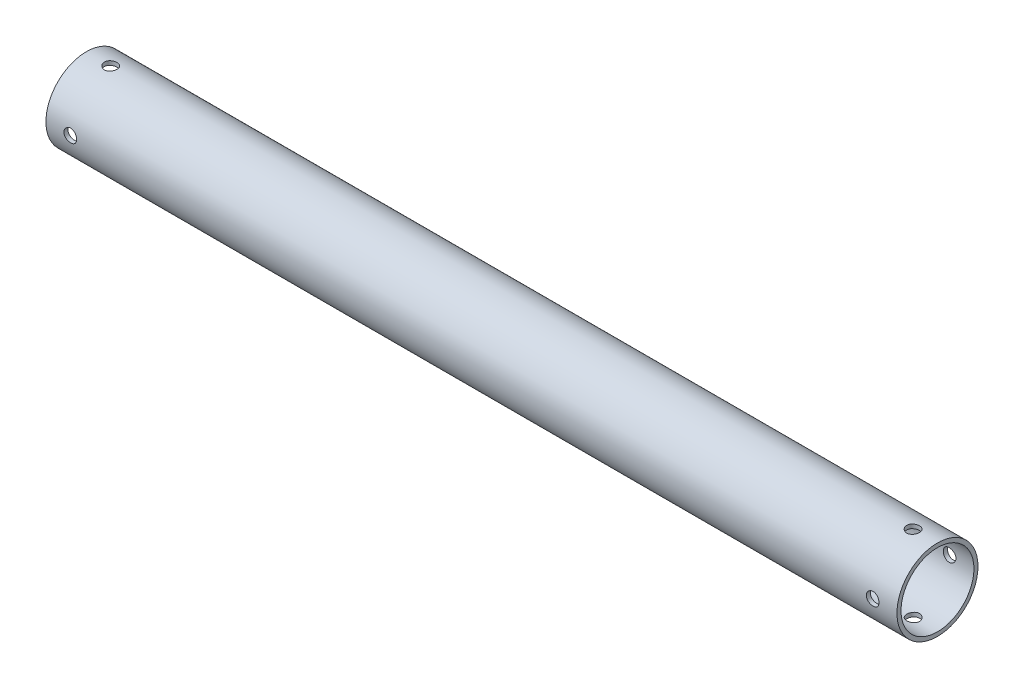
SolidWorks part; units mm, degrees
material "PC High Viscosity"
ref_plane "Front Plane" through (0, 0, 0) normal (0, 0, 1) x (1, 0, 0)
ref_plane "Top Plane" through (0, 0, 0) normal (0, 1, 0) x (1, 0, 0)
ref_plane "Right Plane" through (0, 0, 0) normal (1, 0, 0) x (0, 0, -1)
sketch "Sketch1" plane through (0, 0, 0) normal (1, 0, 0) x (0, 0, -1)
  circle A0 centre (0, 0) radius 15.875
  dimension "D1" = 31.75
extrude "Extrude-Thin1" add sketch "Sketch1" along normal mid plane 333.375 thin thin type one direction reverse wall 1.5875
sketch "Sketch2" plane through (0, 0, 0) normal (0, 0, 1) x (1, 0, 0)
  line L0 (-166.6875, -15.875) -> (166.6875, -15.875) construction
  line L1 (104.4125, -15.875) -> (125.4125, -15.875)
  line L2 (104.4125, -15.875) -> (104.4125, 15.875)
  line L3 (104.4125, 15.875) -> (125.4125, 15.875)
  line L4 (125.4125, -15.875) -> (125.4125, 15.875)
  line L5 (166.6875, 15.875) -> (-166.6875, 15.875) construction
  line L6 (166.6875, -15.875) -> (166.6875, 15.875) construction
  line L7 (0, 0) -> (0, 11.1276) construction
  line L8 (-125.4125, -15.875) -> (-125.4125, 15.875)
  line L9 (-104.4125, 15.875) -> (-125.4125, 15.875)
  line L10 (-104.4125, -15.875) -> (-104.4125, 15.875)
  line L11 (-104.4125, -15.875) -> (-125.4125, -15.875)
  line L13 (166.6875, -15.875) -> (164.3634, -15.875)
  line L14 (166.6875, -15.875) -> (166.6875, 15.875)
  line L15 (166.6875, 15.875) -> (164.3634, 15.875)
  line L16 (164.3634, -15.875) -> (164.3634, 15.875)
  dimension "D1" = 41.275
  dimension "D2" = 21
  dimension "D3" = 2.3241
sketch "Sketch3" plane through (0, 0, 0) normal (0, 0, 1) x (1, 0, 0)
  line L0 (166.6875, -14.2875) -> (166.6875, 14.2875) construction
  line L1 (-166.6875, 15.875) -> (-166.6875, -15.875) construction
  circle A0 centre (157.1625, 0) radius 2.4892
  circle A1 centre (-157.1625, 0) radius 2.4892
  dimension "D1" = 4.9784
  dimension "D2" = 9.525
  dimension "D3" = 9.525
extrude "Cut-Extrude1" cut sketch "Sketch3" against normal through all both and the other way through all
sketch "Sketch4" plane through (0, 0, 0) normal (0, 1, 0) x (1, 0, 0)
  line L0 (166.6875, -14.2875) -> (166.6875, 14.2875) construction
  line L1 (0, 15.875) -> (0, -15.875) construction
  line L2 (-154.6733, -15.875) -> (154.6733, -15.875) construction
  line L3 (154.6733, 15.875) -> (-154.6733, 15.875) construction
  circle A0 centre (157.1625, 0) radius 2.4892
  circle A1 centre (-157.1625, 0) radius 2.4892
  point P13 (-153.4268, 21.7052)
  dimension "D1" = 4.9784
  dimension "D2" = 9.525
extrude "Cut-Extrude2" cut sketch "Sketch4" against normal through all both and the other way through all
equation "\"D2@Sketch2\"=21mm"
